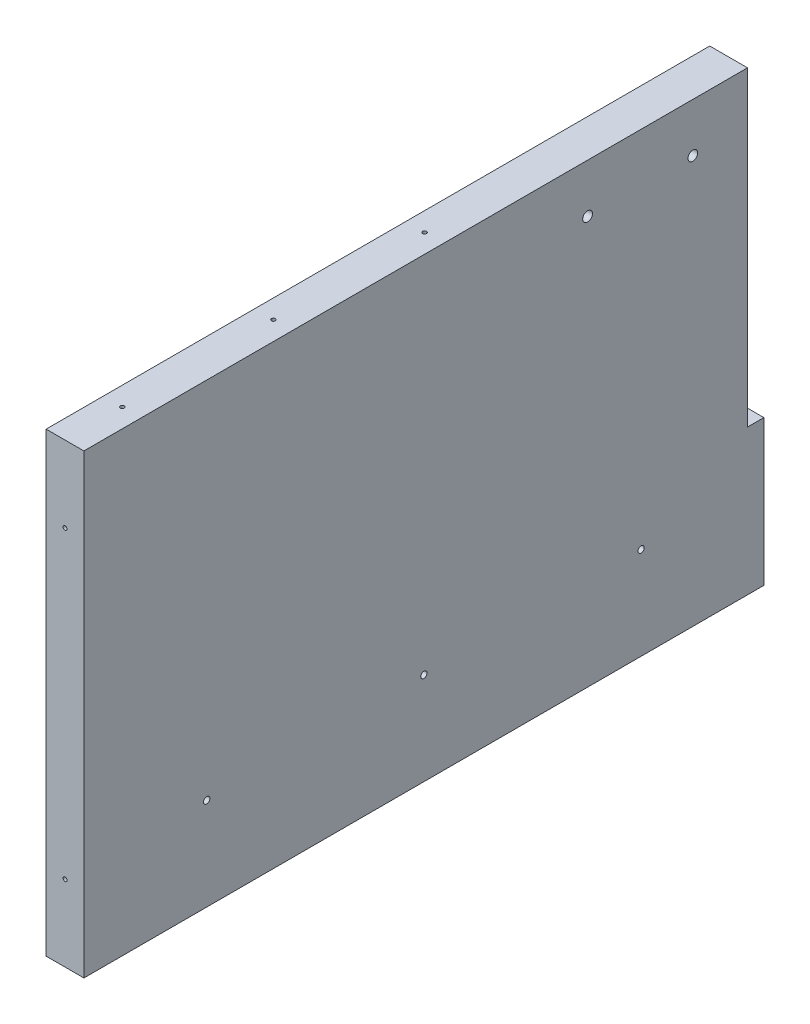
SolidWorks part; units mm, degrees
material "MDF"
ref_plane "Front Plane" through (0, 0, 0) normal (0, 0, 1) x (1, 0, 0)
ref_plane "Top Plane" through (0, 0, 0) normal (0, 1, 0) x (1, 0, 0)
ref_plane "Right Plane" through (0, 0, 0) normal (1, 0, 0) x (0, 0, -1)
sketch "Sketch1" plane through (0, 0, 0) normal (0, 0, 1) x (1, 0, 0)
  line L0 (-296.7037, -233.3625) -> (-271.672, -233.3625) construction
  line L1 (-290.722, -3.175) -> (-271.672, -3.175)
  line L2 (-290.722, -3.175) -> (-290.722, -233.3625)
  line L3 (-290.722, -233.3625) -> (-271.672, -233.3625)
  line L4 (-271.672, -3.175) -> (-271.672, -233.3625)
  dimension "D1" = 19.05
extrude "Boss-Extrude1" add sketch "Sketch1" along normal blind 342.9
sketch "Sketch2" plane through (0, 0, 0) normal (0, 0, 1) x (1, 0, 0)
  line L1 (-199.4987, -156.8808) -> (-434.4987, -156.8808) construction
  line L2 (-271.672, -3.175) -> (-290.722, -3.175) construction
  line L3 (-271.672, -156.8808) -> (-290.722, -156.8808) construction
  line L4 (-271.672, -160.0558) -> (-290.722, -160.0558)
  line L5 (-290.722, -3.175) -> (-271.672, -3.175)
  line L6 (-271.672, -160.0558) -> (-271.672, -3.175)
  line L9 (-290.722, -3.175) -> (-290.722, -160.0558)
  line L10 (-271.672, -233.3625) -> (-271.672, -3.175) construction
  line L11 (-290.722, -3.175) -> (-290.722, -233.3625) construction
  line L12 (-199.4987, -160.0558) -> (-434.4987, -160.0558) construction
  line L13 (-199.4987, -156.8808) -> (-434.4987, -156.8808) construction
  dimension "D1" = 3.175
extrude "Cut-Extrude1" cut sketch "Sketch2" along normal blind 8.255
hole_wizard "15/64 (0.23438) Diameter Hole3" positions "Sketch7" profile "Sketch8" hole size "15/64" standard "ANSI Inch"
sketch "Sketch7" plane through (-182.4037, 1936.854, -6.35) normal (0, 0, -1) x (1, 0, 0)
  point P0 (-262.8265, 2051.0885)
  point P3 (-262.8265, 2014.0687)
  point P6 (-262.8265, 1977.0488)
  point P9 (-98.7933, 2115.9598)
  point P12 (-98.7933, 2151.1665)
  point P15 (-44.6341, 2123.544)
  point P18 (0, 2123.544)
  point P21 (44.6341, 2123.544)
sketch "Sketch8" plane through (-445.2302, -114.2346, -6.35) normal (1, 0, 0) x (0, 1, 0)
  line L0 (0, 0) -> (0, 14.4885)
  line L1 (0, 14.4885) -> (2.9766, 12.7)
  line L2 (2.9766, 12.7) -> (2.9766, 0)
  line L3 (2.9766, 0) -> (0, 0)
  line L4 (0, 14.4885) -> (-2.9766, 12.7) construction
  line L5 (0, -6.35) -> (0, 107.95) construction
  dimension "Hole Dia." = 5.9533
  dimension "Hole Depth" = 12.7
  dimension "Drill Angle" = 118
hole_wizard "5/64 (0.07813) Diameter Hole1" positions "Sketch9" profile "Sketch10" hole size "5/64" standard "ANSI Inch"
sketch "Sketch9" plane through (-182.4037, 15.875, 6471.4599) normal (0, 1, 0) x (1, 0, 0)
  line L1 (-1.27, 6109.5099) -> (-1.27, 6338.7449) construction
  point P0 (-262.8265, 6157.4524)
  point P6 (-98.7933, 6157.4524)
  point P18 (-262.8265, 6233.6524)
  point P19 (-98.7933, 6233.6524)
  point P22 (-262.8265, 6309.8524)
  point P23 (-98.7933, 6309.8524)
  point P24 (-267.97, 6119.0349)
  point P34 (-115.57, 6119.0349)
  point P37 (-1.27, 6119.0349)
  point P40 (113.03, 6119.0349)
  point P44 (265.43, 6119.0349)
  point P55 (96.2533, 6309.8524)
  point P56 (260.2865, 6309.8524)
  point P59 (96.2533, 6233.6524)
  point P60 (260.2865, 6233.6524)
  point P63 (96.2533, 6157.4524)
  point P64 (260.2865, 6157.4524)
sketch "Sketch10" plane through (-445.2302, 15.875, 314.0075) normal (1, 0, 0) x (0, 0, 1)
  line L0 (0, 0) -> (0, 38.6962)
  line L1 (0, 38.6962) -> (0.9923, 38.1)
  line L2 (0.9923, 38.1) -> (0.9923, 4.7024)
  line L3 (0.9923, 4.7024) -> (5.08, 0)
  line L4 (5.08, 0) -> (0, 0)
  line L5 (-0.9923, 4.7024) -> (-5.08, 0) construction
  line L6 (0, 38.6962) -> (-0.9923, 38.1) construction
  line L7 (0, -6.35) -> (0, 107.95) construction
  dimension "Hole Dia." = 1.9845
  dimension "Hole Depth" = 38.1
  dimension "Near C'Sink Dia." = 10.16
  dimension "Near C'Sink Angle" = 82
  dimension "Drill Angle" = 118
hole_wizard "5/64 (0.07813) Diameter Hole2" positions "Sketch11" profile "Sketch12" hole size "5/64" standard "ANSI Inch"
sketch "Sketch11" plane through (-182.4037, 1936.854, 361.95) normal (0, 0, 1) x (-1, 0, 0)
  line L23 (262.8265, 2088.1084) -> (262.8265, 2038.7486)
  line L24 (262.8265, 2038.7486) -> (262.8265, 1989.3888)
  line L25 (262.8265, 1989.3888) -> (262.8265, 2038.7486)
  line L26 (262.8265, 2038.7486) -> (262.8265, 1989.3888)
  line L27 (262.8265, 1989.3888) -> (262.8265, 1940.029)
  line L33 (98.7933, 2170.2165) -> (98.7933, 2131.8519)
  line L35 (98.7933, 2131.8519) -> (98.7933, 2093.4873)
  line L36 (98.7933, 2093.4873) -> (98.7933, 2055.1227)
  line L37 (98.7933, 2055.1227) -> (98.7933, 2016.7581)
  line L38 (98.7933, 2016.7581) -> (98.7933, 1978.3935)
  line L39 (98.7933, 1978.3935) -> (98.7933, 1940.029)
  line L44 (89.2683, 2123.544) -> (53.561, 2123.544)
  line L46 (53.561, 2123.544) -> (17.8537, 2123.544)
  line L47 (17.8537, 2123.544) -> (-17.8537, 2123.544)
  line L48 (-17.8537, 2123.544) -> (-53.561, 2123.544)
  line L49 (-53.561, 2123.544) -> (-89.2683, 2123.544)
  line L53 (0, 2170.2165) -> (0.2777, 1940.029) construction
  line L55 (-98.3301, 1978.1557) -> (-98.2375, 1939.7912)
  line L56 (-98.4227, 2016.5202) -> (-98.3301, 1978.1557)
  line L57 (-98.5153, 2054.8846) -> (-98.4227, 2016.5202)
  line L58 (-98.6078, 2093.2491) -> (-98.5153, 2054.8846)
  line L59 (-98.7004, 2131.6136) -> (-98.6078, 2093.2491)
  line L60 (-98.793, 2169.978) -> (-98.7004, 2131.6136)
  line L61 (-262.3894, 1988.755) -> (-262.2702, 1939.3954)
  line L62 (-262.5085, 2038.1147) -> (-262.3894, 1988.755)
  line L63 (-262.3894, 1988.755) -> (-262.5085, 2038.1147)
  line L64 (-262.5085, 2038.1147) -> (-262.3894, 1988.755)
  line L65 (-262.6276, 2087.4744) -> (-262.5085, 2038.1147)
  point P71 (262.8265, 1964.7089)
  point P79 (262.8265, 2063.4285)
  point P95 (98.7933, 2131.8519)
  point P103 (98.7933, 1978.3935)
  point P126 (53.561, 2123.544)
  point P134 (-53.561, 2123.544)
  point P162 (-98.3301, 1978.1557)
  point P166 (-98.7004, 2131.6136)
  point P167 (-262.568, 2062.7945)
  point P169 (-262.3298, 1964.0752)
sketch "Sketch12" plane through (79.926, -27.2212, 361.95) normal (1, 0, 0) x (0, -1, 0)
  line L0 (0, 0) -> (0, 38.6962)
  line L1 (0, 38.6962) -> (0.9923, 38.1)
  line L2 (0.9923, 38.1) -> (0.9923, 4.7024)
  line L3 (0.9923, 4.7024) -> (5.08, 0)
  line L4 (5.08, 0) -> (0, 0)
  line L5 (-0.9923, 4.7024) -> (-5.08, 0) construction
  line L6 (0, 38.6962) -> (-0.9923, 38.1) construction
  line L7 (0, -6.35) -> (0, 107.95) construction
  dimension "Hole Dia." = 1.9845
  dimension "Hole Depth" = 38.1
  dimension "Near C'Sink Dia." = 10.16
  dimension "Near C'Sink Angle" = 82
  dimension "Drill Angle" = 118
hole_wizard "1/8 (0.125) Diameter Hole1" positions "Sketch13" profile "Sketch14" hole size "1/8" standard "ANSI Inch" end condition up to next
sketch "Sketch13" plane through (-290.722, 0, 0) normal (-1, 0, 0) x (0, 0, 1)
  line L4 (317.5, -186.69) -> (280.9875, -186.69)
  line L5 (317.5, -193.04) -> (317.5, -180.34) construction
  line L6 (280.9875, -186.69) -> (244.475, -186.69)
  line L7 (244.475, -186.69) -> (207.9625, -186.69)
  line L8 (207.9625, -186.69) -> (171.45, -186.69)
  line L9 (171.45, -186.69) -> (134.9375, -186.69)
  line L10 (134.9375, -186.69) -> (98.425, -186.69)
  line L11 (98.425, -186.69) -> (61.9125, -186.69)
  line L12 (61.9125, -186.69) -> (25.4, -186.69)
  line L13 (25.4, -180.34) -> (25.4, -193.04) construction
  point P10 (280.9875, -186.69)
  point P18 (171.45, -186.69)
  point P24 (61.9125, -186.69)
sketch "Sketch14" plane through (-290.722, -186.69, 61.9125) normal (0, 1, 0) x (0, 0, 1)
  line L0 (0, 0) -> (0, 19.05)
  line L1 (0, 19.05) -> (1.5875, 19.05)
  line L2 (1.5875, 19.05) -> (1.5875, 3.4925)
  line L3 (1.5875, 3.4925) -> (5.08, 0)
  line L5 (5.08, 0) -> (0, 0)
  line L6 (-1.5875, 3.4925) -> (-5.08, 0) construction
  line L11 (0, -6.35) -> (0, 107.95) construction
  dimension "Thru Hole Dia." = 3.175
  dimension "Thru Hole Depth" = 19.05
  dimension "Near C'Sink Dia." = 10.16
  dimension "Near C'Sink Angle" = 90
hole_wizard "#8 Clearance Hole1" positions "Sketch15" profile "Sketch16" hole size "#8" standard "ANSI Inch" end condition up to next
sketch "Sketch15" plane through (-271.672, 0, 0) normal (1, 0, 0) x (0, 0, -1)
  point P0 (-88.9, -27.7495)
  point P2 (-35.8275, -27.7495)
sketch "Sketch16" plane through (-271.672, -27.7495, 88.9) normal (0, 1, 0) x (0, 0, -1)
  line L0 (0, 0) -> (0, 19.05)
  line L1 (0, 19.05) -> (2.4574, 19.05)
  line L2 (2.4574, 19.05) -> (2.4574, 0)
  line L5 (2.4574, 0) -> (0, 0)
  line L11 (0, -6.35) -> (0, 107.95) construction
  dimension "Thru Hole Dia." = 4.9149
  dimension "Thru Hole Depth" = 19.05
